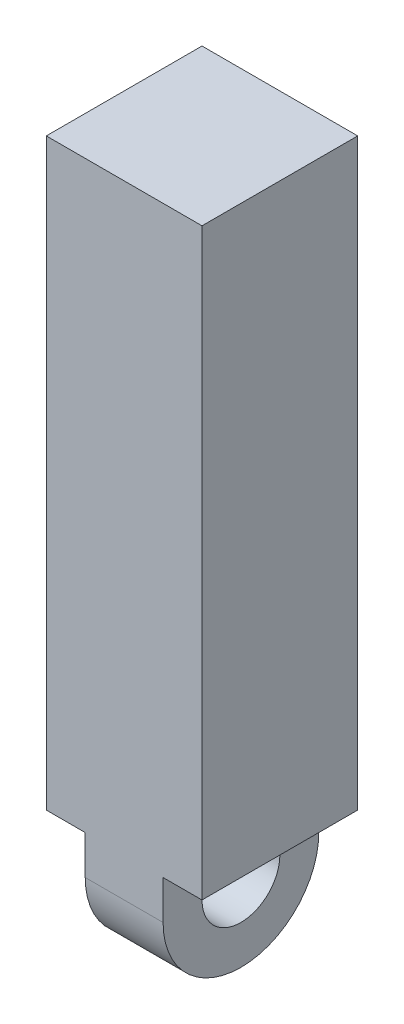
SolidWorks part; units mm, degrees
ref_plane "Front Plane" through (0, 0, 0) normal (0, 0, 1) x (1, 0, 0)
ref_plane "Top Plane" through (0, 0, 0) normal (0, 1, 0) x (1, 0, 0)
ref_plane "Right Plane" through (0, 0, 0) normal (1, 0, 0) x (0, 0, -1)
sketch "Sketch1" plane through (0, 0, 0) normal (0, 1, 0) x (1, 0, 0)
  line L1 (-50.8, -50.8) -> (50.8, -50.8)
  line L2 (-50.8, -50.8) -> (-50.8, 50.8)
  line L3 (-50.8, 50.8) -> (50.8, 50.8)
  line L4 (50.8, -50.8) -> (50.8, 50.8)
  line L5 (-50.8, -50.8) -> (50.8, 50.8) construction
  line L6 (-50.8, 50.8) -> (50.8, -50.8) construction
  point P0 (0, 0)
  dimension "D1" = 101.6
  dimension "D2" = 101.6
extrude "Boss-Extrude1" add sketch "Sketch1" along normal blind 457.2
sketch "Sketch2" plane through (0, 0, 50.8) normal (0, 0, 1) x (1, 0, 0)
  line L1 (-50.8, 0) -> (-25.4, 0)
  line L2 (-50.8, 0) -> (-50.8, 76.2)
  line L3 (-50.8, 76.2) -> (-25.4, 76.2)
  line L4 (-25.4, 0) -> (-25.4, 76.2)
  line L5 (50.8, 0) -> (25.4, 0)
  line L6 (50.8, 0) -> (50.8, 76.2)
  line L7 (50.8, 76.2) -> (25.4, 76.2)
  line L8 (25.4, 0) -> (25.4, 76.2)
  dimension "D1" = 76.2
  dimension "D2" = 25.4
  dimension "D3" = 25.4
  dimension "D4" = 76.2
extrude "Cut-Extrude1" cut sketch "Sketch2" against normal through all
fillet "Fillet1" radius 50.8 2 edges at (0, 0, -50.8) (0, 0, 50.8)
sketch "Sketch3" plane through (-25.4, 0, 0) normal (-1, 0, 0) x (0, 0, 1)
  circle A0 centre (0, 50.8) radius 25.4
  dimension "D2" = 50.8
  dimension "D1" = 50.8
extrude "Cut-Extrude2" cut sketch "Sketch3" against normal through all
